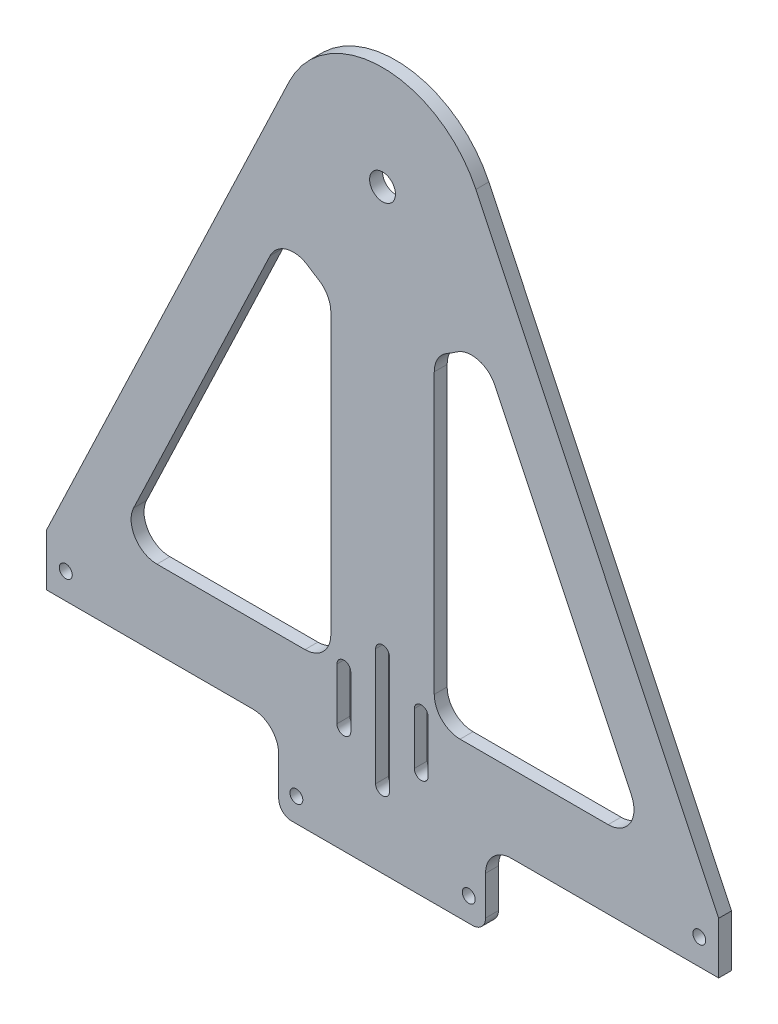
SolidWorks part; units mm, degrees
material "Titanium Ti-8Al-1Mo-1V"
ref_plane "Front Plane" through (0, 0, 0) normal (0, 0, 1) x (1, 0, 0)
ref_plane "Top Plane" through (0, 0, 0) normal (0, 1, 0) x (1, 0, 0)
ref_plane "Right Plane" through (0, 0, 0) normal (1, 0, 0) x (0, 0, -1)
sketch "Sketch1" plane through (0, 0, 0) normal (0, 0, 1) x (1, 0, 0)
  line L0 (0, -58.42) -> (0, 58.42) construction
  line L2 (-82.55, 55.7897) -> (-82.55, -52.07)
  line L3 (-76.2, -58.42) -> (76.2, -58.42)
  line L4 (82.55, 55.7897) -> (82.55, -52.07)
  line L5 (-82.55, 58.42) -> (82.55, -58.42) construction
  line L6 (-82.55, -58.42) -> (82.55, 58.42) construction
  line L7 (-80.6901, 60.2799) -> (-75.4296, 65.5404)
  line L8 (-70.9395, 67.4003) -> (-50.8, 67.4003)
  line L9 (-46.3099, 65.5404) -> (-41.0494, 60.2799)
  line L10 (46.3099, 65.5404) -> (41.0494, 60.2799)
  line L11 (70.9395, 67.4003) -> (50.8, 67.4003)
  line L12 (80.6901, 60.2799) -> (75.4296, 65.5404)
  line L13 (-73.5697, 67.4003) -> (-82.55, 67.4003) construction
  line L14 (-82.55, 67.4003) -> (-82.55, 58.42) construction
  line L15 (-36.5592, 58.42) -> (0, 58.42)
  line L16 (0, 58.42) -> (36.5592, 58.42)
  circle A0 centre (-77.7875, -35.052) radius 1.5875
  circle A1 centre (-77.7875, -11.684) radius 1.5875
  circle A2 centre (-77.7875, 11.684) radius 1.5875
  circle A3 centre (-77.7875, 35.052) radius 1.5875
  circle A4 centre (77.7875, 35.052) radius 1.5875
  circle A5 centre (77.7875, 11.684) radius 1.5875
  circle A6 centre (77.7875, -11.684) radius 1.5875
  circle A7 centre (77.7875, -35.052) radius 1.5875
  arc A8 (82.55, 55.7897) -> (80.6901, 60.2799) centre (76.2, 55.7897) ccw
  arc A9 (75.4296, 65.5404) -> (70.9395, 67.4003) centre (70.9395, 61.0503) ccw
  arc A10 (46.3099, 65.5404) -> (50.8, 67.4003) centre (50.8, 61.0503) cw
  arc A11 (41.0494, 60.2799) -> (36.5592, 58.42) centre (36.5592, 64.77) cw
  arc A12 (-36.5592, 58.42) -> (-41.0494, 60.2799) centre (-36.5592, 64.77) cw
  arc A13 (-46.3099, 65.5404) -> (-50.8, 67.4003) centre (-50.8, 61.0503) ccw
  arc A14 (-70.9395, 67.4003) -> (-75.4296, 65.5404) centre (-70.9395, 61.0503) ccw
  arc A15 (-82.55, 55.7897) -> (-80.6901, 60.2799) centre (-76.2, 55.7897) cw
  arc A16 (76.2, -58.42) -> (82.55, -52.07) centre (76.2, -52.07) ccw
  arc A17 (-76.2, -58.42) -> (-82.55, -52.07) centre (-76.2, -52.07) cw
  circle A18 centre (-70.9395, 61.0503) radius 1.5875
  circle A19 centre (-50.8, 61.0503) radius 1.5875
  circle A20 centre (50.8, 61.0503) radius 1.5875
  circle A21 centre (70.9395, 61.0503) radius 1.5875
  point P0 (0, 0)
  point P36 (73.5697, 67.4003)
  point P39 (48.1697, 67.4003)
  point P42 (39.1895, 58.42)
  point P45 (-39.1895, 58.42)
  point P48 (-48.1697, 67.4003)
  dimension "D3" = 3.175
  dimension "D11" = 6.35
  dimension "D12" = 6.35
  dimension "D13" = 3.175
  dimension "D14" = 3.175
  dimension "D1" = 165.1
  dimension "D2" = 116.84
  dimension "D4" = 23.368
  dimension "D5" = 4.7625
  dimension "D7" = 46.736
  dimension "D8" = 12.7
  dimension "D9" = 135
  dimension "D10" = 25.4
  dimension "D6" = 4
extrude "Boss-Extrude1" [suppressed] add sketch "Sketch1" along normal blind 1.5
sketch "Sketch2" [suppressed] plane through (0, 0, 1.5) normal (0, 0, 1) x (1, 0, 0)
  line L0 (0, -45.72) -> (0, 6.3634) construction
  line L1 (0, -58.42) -> (0, 63.5) construction
  line L3 (-82.55, 1.8599) -> (82.55, 1.8599) construction
  line L4 (-82.55, 55.7897) -> (-82.55, -52.07) construction
  line L5 (82.55, -52.07) -> (82.55, 55.7897) construction
  line L7 (-76.2, -58.42) -> (76.2, -58.42) construction
  circle A0 centre (0, -45.72) radius 1.9062
  circle A1 centre (0, 6.3634) radius 1.9062
  dimension "D2" = 3.8125
  dimension "D3" = 3.8125
  dimension "D1" = 52.0834
  dimension "D4" = 12.7
extrude "Cut-Extrude1" [suppressed] cut sketch "Sketch2" against normal through all
sketch "Sketch3" [suppressed] plane through (0, 0, 1.5) normal (0, 0, 1) x (1, 0, 0)
  line L0 (0, 50.8) -> (0, 30.8) construction
  line L1 (-10, 40.8) -> (10, 40.8) construction
  line L2 (-10, 40.8) -> (0, 50.8) construction
  line L3 (0, 50.8) -> (10, 40.8) construction
  line L4 (10, 40.8) -> (0, 30.8) construction
  line L5 (0, 30.8) -> (-10, 40.8) construction
  line L6 (0, 63.5) -> (0, -58.42) construction
  line L8 (-76.2, -58.42) -> (76.2, -58.42) construction
  circle A0 centre (0, 50.8) radius 1.8669
  circle A1 centre (-10, 40.8) radius 1.8669
  circle A2 centre (0, 30.8) radius 1.8669
  circle A3 centre (10, 40.8) radius 1.8669
  dimension "D1" = 3.7338
  dimension "D2" = 12.7
extrude "Cut-Extrude2" [suppressed] cut sketch "Sketch3" against normal through all
sketch "Sketch4" [suppressed] plane through (0, 0, 1.5) normal (0, 0, 1) x (1, 0, 0)
  line L0 (0, 58.42) -> (0, -58.42) construction
  line L1 (36.5592, 58.42) -> (-36.5592, 58.42) construction
  line L2 (-76.2, -58.42) -> (76.2, -58.42) construction
  line L5 (0, 33.045) -> (0, 52.045) construction
  line L6 (-9.5, 42.545) -> (9.5, 42.545) construction
  circle A14 centre (0, 42.545) radius 8 construction
  circle A15 centre (0, 42.545) radius 9.5 construction
  circle A16 centre (0, 50.545) radius 1.5
  circle A17 centre (0, 34.545) radius 1.5
  circle A18 centre (-9.5, 42.545) radius 1.5
  circle A19 centre (9.5, 42.545) radius 1.5
  dimension "D1" = 15.875
  dimension "D3" = 16
  dimension "D4" = 19
  dimension "D5" = 3
  dimension "D6" = 3
  dimension "D7" = 3
  dimension "D8" = 3
extrude "Cut-Extrude3" [suppressed] cut sketch "Sketch4" against normal through all
sketch "Sketch5" plane through (0, 0, 0) normal (0, 0, 1) x (1, 0, 0)
  line L0 (0, 58.42) -> (0, 26.67) construction
  line L1 (-82.55, 58.42) -> (82.55, 58.42) construction
  line L2 (-82.55, 58.42) -> (-82.55, 45.72)
  line L4 (82.55, 58.42) -> (82.55, 45.72)
  line L5 (82.55, 58.42) -> (22.9335, 183.6386)
  line L8 (77.7875, 45.72) -> (77.7875, 58.42) construction
  line L11 (0, -48.26) -> (0, -46.3538) construction
  line L12 (0, 58.42) -> (0, 172.72) construction
  line L14 (-82.55, 45.72) -> (-31.849, 45.72)
  line L15 (-22.324, 26.67) -> (22.126, 26.67)
  line L16 (-25.499, 29.845) -> (-25.499, 39.37)
  line L17 (25.301, 29.845) -> (25.301, 39.37)
  line L18 (31.651, 45.72) -> (82.55, 45.72)
  line L19 (-82.55, 58.42) -> (-22.9335, 183.6386)
  line L20 (-77.7875, 45.72) -> (-77.7875, 58.42) construction
  line L23 (0, -0.6801) -> (0, 0) construction
  line L24 (0, 26.67) -> (0, 58.42) construction
  line L26 (0, 58.42) -> (-82.55, 58.42) construction
  line L27 (-61.138, 73.8497) -> (-27.6156, 144.2603)
  line L28 (0, -48.26) -> (0, -46.3538) construction
  line L37 (68.4841, 58.42) -> (11.4667, 178.1793) construction
  line L38 (31.651, 58.42) -> (68.4841, 58.42) construction
  line L39 (12.601, 39.37) -> (12.601, 39.37) construction
  line L40 (-12.799, 39.37) -> (12.601, 39.37) construction
  line L41 (-12.799, 39.37) -> (-12.799, 39.37) construction
  line L42 (-68.4841, 58.42) -> (-31.849, 58.42) construction
  line L43 (-12.7, 71.12) -> (-12.7, 139.7244)
  line L44 (-68.4841, 58.42) -> (-11.4667, 178.1793) construction
  line L45 (68.4841, 58.42) -> (68.4841, 58.42) construction
  line L46 (-55.4047, 64.77) -> (-19.05, 64.77)
  line L47 (-12.7, 58.42) -> (-12.7, 172.72) construction
  line L48 (19.05, 64.77) -> (55.4047, 64.77) construction
  line L49 (-82.55, 64.77) -> (82.55, 64.77) construction
  line L50 (-68.4841, 58.42) -> (-68.4841, 58.42) construction
  line L51 (61.138, 73.8497) -> (27.6156, 144.2603)
  line L52 (55.4047, 64.77) -> (19.05, 64.77)
  line L53 (12.7, 71.12) -> (12.7, 139.7244)
  line L54 (-11.2, 52.9151) -> (-11.2, 65.6151)
  line L55 (-7.8, 52.9151) -> (-7.8, 65.6151)
  line L56 (-1.7, 44.9151) -> (-1.7, 73.6151)
  line L57 (1.7, 44.9151) -> (1.7, 73.6151)
  line L58 (7.8, 52.9151) -> (7.8, 65.6151)
  line L59 (11.2, 52.9151) -> (11.2, 65.6151)
  arc A12 (-25.499, 39.37) -> (-31.849, 45.72) centre (-31.849, 39.37) ccw
  arc A13 (25.301, 39.37) -> (31.651, 45.72) centre (31.651, 39.37) cw
  arc A14 (25.301, 29.845) -> (22.126, 26.67) centre (22.126, 29.845) cw
  arc A15 (-25.499, 29.845) -> (-22.324, 26.67) centre (-22.324, 29.845) ccw
  circle A16 centre (-77.7875, 52.07) radius 1.5875
  circle A17 centre (77.7875, 52.07) radius 1.5875
  arc A18 (22.9335, 183.6386) -> (-22.9335, 183.6386) centre (0, 172.72) ccw
  circle A19 centre (0, 172.72) radius 25.4 construction
  arc A25 (11.4667, 178.1793) -> (-11.4667, 178.1793) centre (0, 172.72) ccw construction
  arc A26 (12.601, 39.37) -> (31.651, 58.42) centre (31.651, 39.37) cw construction
  arc A27 (-12.799, 39.37) -> (-31.849, 58.42) centre (-31.849, 39.37) ccw construction
  arc A28 (12.601, 39.37) -> (12.601, 39.37) centre (12.601, 39.37) cw construction
  arc A29 (-12.799, 39.37) -> (-12.799, 39.37) centre (-12.799, 39.37) ccw construction
  arc A30 (-18.2352, 146.7288) -> (-15.875, 145.2237) centre (0, 172.72) ccw
  arc A31 (-18.2352, 146.7288) -> (-27.6156, 144.2603) centre (-21.8822, 141.5306) ccw
  circle A32 centre (0, 172.72) radius 31.75 construction
  arc A33 (-15.875, 145.2237) -> (-12.7, 139.7244) centre (-19.05, 139.7244) cw
  arc A34 (-19.05, 64.77) -> (-12.7, 71.12) centre (-19.05, 71.12) ccw
  arc A35 (-55.4047, 64.77) -> (-61.138, 73.8497) centre (-55.4047, 71.12) cw
  arc A36 (15.875, 145.2237) -> (12.7, 139.7244) centre (19.05, 139.7244) ccw
  arc A37 (18.2352, 146.7288) -> (15.875, 145.2237) centre (0, 172.72) cw
  arc A38 (18.2352, 146.7288) -> (27.6156, 144.2603) centre (21.8822, 141.5306) cw
  arc A39 (55.4047, 64.77) -> (61.138, 73.8497) centre (55.4047, 71.12) ccw
  arc A40 (19.05, 64.77) -> (12.7, 71.12) centre (19.05, 71.12) cw
  circle A57 centre (0, 52.9151) radius 8 construction
  circle A58 centre (0, 52.9151) radius 9.5 construction
  arc A59 (7.8, 52.9151) -> (11.2, 52.9151) centre (9.5, 52.9151) ccw
  arc A60 (-11.2, 52.9151) -> (-7.8, 52.9151) centre (-9.5, 52.9151) ccw
  arc A62 (-1.7, 44.9151) -> (1.7, 44.9151) centre (0, 44.9151) ccw
  arc A63 (-7.8, 65.6151) -> (-11.2, 65.6151) centre (-9.5, 65.6151) ccw
  arc A64 (11.2, 65.6151) -> (7.8, 65.6151) centre (9.5, 65.6151) ccw
  arc A65 (1.7, 73.6151) -> (-1.7, 73.6151) centre (0, 73.6151) ccw
  circle A66 centre (-21.1667, 32.5034) radius 1.5875
  circle A67 centre (21.1667, 32.5034) radius 1.5875
  circle A68 centre (0, 172.72) radius 3.175
  point P0 (0, 0)
  point P52 (25.301, 45.72)
  point P55 (25.301, 26.67)
  point P58 (-25.499, 26.67)
  point P68 (30.3627, 182.0028)
  dimension "D17" = 6.35
  dimension "D18" = 6.35
  dimension "D19" = 3.175
  dimension "D20" = 3.175
  dimension "D21" = 3.175
  dimension "D4" = 50.8
  dimension "D24" = 6.35
  dimension "D25" = 16
  dimension "D26" = 19
  dimension "D27" = 3.4
  dimension "D28" = 3.4
  dimension "D30" = 3.4
  dimension "D31" = 3.4
  dimension "D32" = 3.4
  dimension "D35" = 3.4
  dimension "D36" = 3.175
  dimension "D9" = 6.35
  dimension "D14" = 12.7
  dimension "D15" = 50.8
  dimension "D16" = 19.05
  dimension "D22" = 6.35
  dimension "D3" = 114.3
  dimension "D33" = 12.7
  dimension "D34" = 12.7
  dimension "D8" = 25.9166
  dimension "D6" = 6.35
  dimension "D7" = 12.7
  dimension "D23" = 6.35
extrude "Boss-Extrude2" add sketch "Sketch5" along normal blind 3.175
equation "\"Top Plate Width\" = 4.5in"
equation "\"Plate Width\" = 3.5in"
equation "\"Plate Thickness\" = 0.375in"
equation "\"Num holes\" = 4"
equation "\"Plate Height\" = 1.25in"
equation "\"Plate Clearance Hole Diameter\" = 0.125in"
equation "\"D3@Sketch1\"=\"Plate Clearance Hole Diameter\""
equation "\"Hole Spacing\"= \"Plate Width\" / ( \"Num holes\" + 1 )"
equation "\"Plate Tap Hole Diameter\" = 0.116in"
equation "\"Bottom Plate Length\" = 6.5in"
equation "\"D21@Sketch5\"=\"Plate Clearance Hole Diameter\""
equation "\"Number Eight Clearance Size\" = 0.177in"
equation "\"Back Brace Height\" = 1.1962912in"
equation "\"Titanium Offset Length\" = 4.5in"
equation "\"Titanium Head Radius\" = 2in"
equation "\"D3@Sketch5\"=\"Titanium Offset Length\""
equation "\"D4@Sketch5\"=\"Titanium Head Radius\""
equation "\"Titanium Plate Border Thickness\" = 0.5in"
equation "\"D5@Sketch5\"=\"Titanium Plate Border Thickness\""
equation "\"D6@Sketch5\"=\"Titanium Plate Border Thickness\" / 2"
equation "\"D23@Sketch5\"=\"Titanium Plate Border Thickness\"/2"
equation "\"slot_hole_length\"=0.75"
